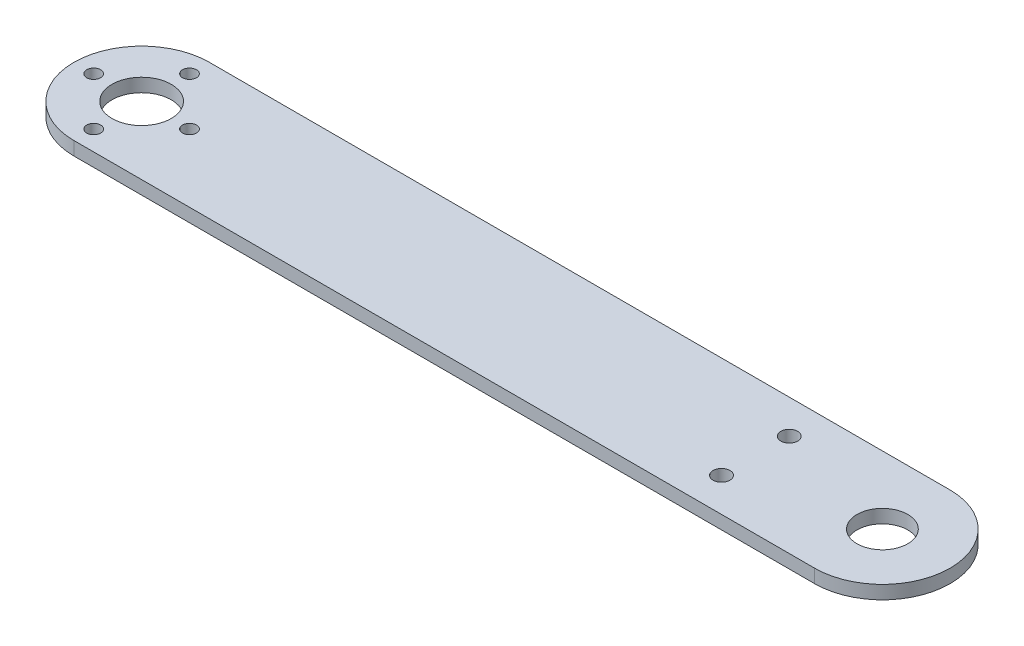
SolidWorks part; units mm, degrees
ref_plane "Front" through (0, 0, 0) normal (0, 0, 1) x (1, 0, 0)
ref_plane "Top" through (0, 0, 0) normal (0, 1, 0) x (1, 0, 0)
ref_plane "Right" through (0, 0, 0) normal (1, 0, 0) x (0, 0, -1)
sketch "Sketch1" plane through (0, 0, 0) normal (0, 1, 0) x (1, 0, 0)
  line L1 (0, 0) -> (175, 0)
  line L2 (0, 0) -> (0, 32)
  line L3 (0, 32) -> (175, 32)
  line L4 (175, 0) -> (175, 32)
  arc A0 (0, 32) -> (0, 0) centre (0, 16) ccw
  arc A1 (175, 32) -> (175, 0) centre (175, 16) cw
  circle A2 centre (0, 16) radius 7
  circle A3 centre (175, 16) radius 6
  dimension "D1" = 32
  dimension "D2" = 175
extrude "Boss-Extrude1" add sketch "Sketch1" along normal blind 3.175 contours A3 L4 L3 L2 A2 L1 | A2 L2 A0 | A3 L4 A1 region at (87.8114, 0, -16) region at (-7.6948, 0, -16) region at (182.4851, 0, -16)
sketch "Sketch2" plane through (0, 3.175, 0) normal (0, 1, 0) x (1, 0, 0)
  line L0 (87.5, 32) -> (87.5, 0)
  line L1 (0, 32) -> (175, 32) construction
  line L2 (0, 0) -> (175, 0) construction
  circle A0 centre (0, 16) radius 11.3137
  circle A1 centre (-11.3137, 16) radius 1.65
  circle A2 centre (11.3137, 16) radius 1.65
  circle A3 centre (0, 27.3137) radius 1.65
  circle A4 centre (0, 4.6863) radius 1.65
  circle A5 centre (175, 4.6863) radius 1.65
  circle A6 centre (163.6863, 16) radius 1.65
  circle A7 centre (186.3137, 16) radius 1.65
  circle A8 centre (175, 27.3137) radius 1.65
extrude "Cut-Extrude1" cut sketch "Sketch2" against normal blind 10 contours A4 | A2 | A3 | A1
sketch "Sketch3" plane through (0, 3.175, 0) normal (0, 1, 0) x (1, 0, 0)
  line L0 (175, 16) -> (145, 16)
  line L1 (145, 16) -> (145, 24)
  line L2 (145, 24) -> (145, 8)
  circle A0 centre (145, 24) radius 2
  circle A1 centre (145, 8) radius 2
  dimension "D1" = 16
  dimension "D2" = 8
  dimension "D3" = 30
extrude "Cut-Extrude2" cut sketch "Sketch3" against normal blind 10 contours A0 | A1 region at (143.6258, 3.175, -25.3742) region at (146.3742, 3.175, -9.3742)
